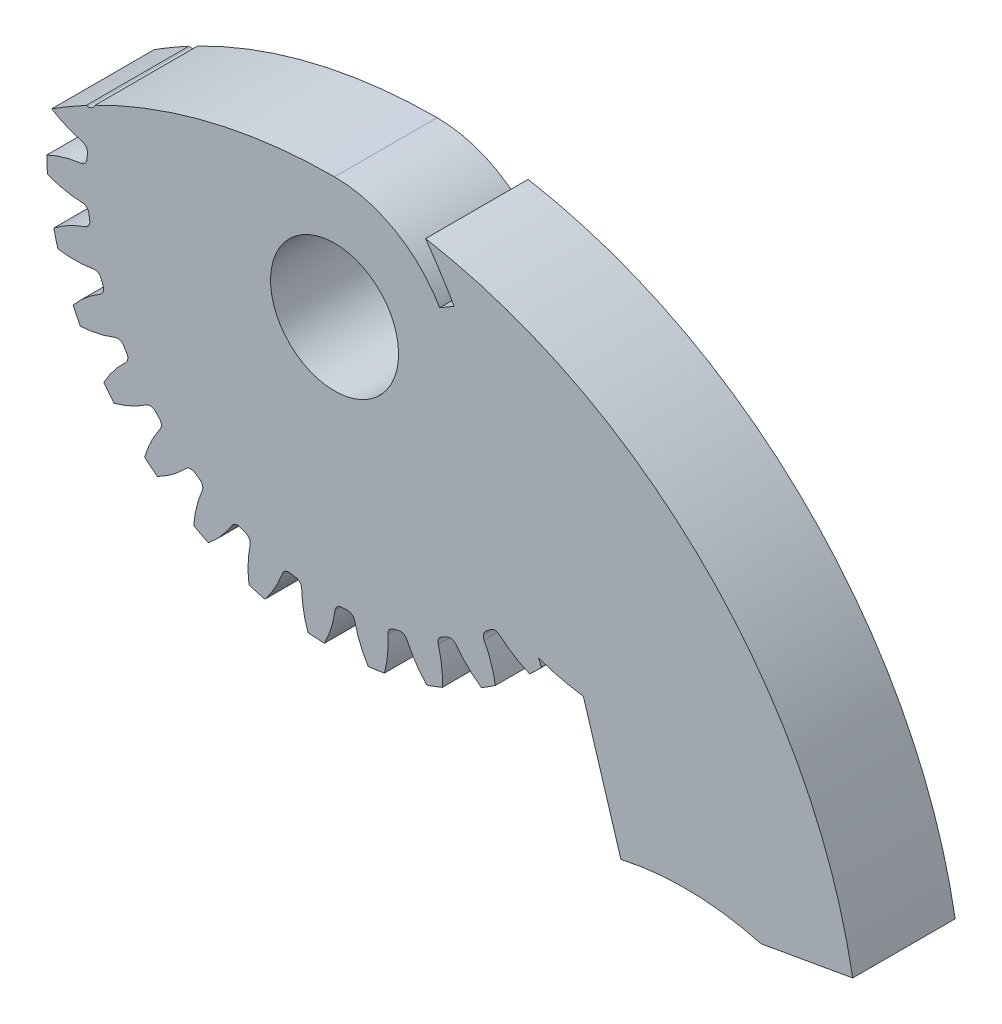
SolidWorks part; units mm, degrees
material "ABS"
ref_plane "Front" through (0, 0, 0) normal (0, 0, 1) x (1, 0, 0)
ref_plane "Top" through (0, 0, 0) normal (0, 1, 0) x (1, 0, 0)
ref_plane "Right" through (0, 0, 0) normal (1, 0, 0) x (0, 0, -1)
sketch "Sketch3" plane through (0, 0, 0) normal (0, 0, 1) x (1, 0, 0)
  circle A0 centre (0, 0) radius 40.64
  dimension "od" = 81.28
extrude "gearBody" add sketch "Sketch3" along normal blind 9.652
sketch "Sketch2" plane through (0, 0, 0) normal (0, 0, 1) x (1, 0, 0)
  line L0 (0, 0) -> (34.0786, 14.1158) construction
  line L1 (45.4751, -11.4855) -> (0, 0) construction
  line L2 (0, 0) -> (36.3143, 0) construction
  line L3 (38.0972, -0.458) -> (37.8451, -4.4001) construction
  line L5 (37.9712, -2.4291) -> (0, 0) construction
  line L7 (0, 0) -> (36.8864, 0) construction
  arc A0 (36.879, -0.7403) -> (36.6727, -3.9649) centre (0, 0) ccw construction
  arc A1 (40.637, 0.4947) -> (40.2427, -5.6687) centre (0, 0) ccw construction
  arc A2 (38.0972, -0.458) -> (37.8451, -4.4001) centre (0, 0) ccw construction
  arc A3 (34.9015, -2.6404) -> (34.9534, -1.8283) centre (0, 0) ccw
  arc A4 (45.4751, -11.4855) -> (35.6466, -3.6712) centre (32.0022, -18.3431) ccw
  arc A5 (45.4751, -11.4855) -> (46.5679, 5.5974) centre (0, 0) ccw
  arc A6 (46.5679, 5.5974) -> (35.8238, -0.9008) centre (34.0786, 14.1158) cw
  arc A7 (34.9534, -1.8283) -> (35.8238, -0.9008) centre (35.9376, -1.8798) cw
  arc A8 (35.6466, -3.6712) -> (34.9015, -2.6404) centre (35.8842, -2.7147) cw
  point P6 (46.5679, 5.5974)
  point P22 (45.4751, -11.4855)
  dimension "baseDia" = 73.7729
  dimension "od" = 81.28
  dimension "pd" = 76.2
  dimension "rd" = 70.0024
  dimension "rFillet" = 0.9855
  dimension "pointX" = 46.5679
  dimension "pointY" = 5.5974
  dimension "CTT" = 3.9421
  dimension "flankCenterAngle" = 22.5
extrude "toothCut" cut sketch "Sketch2" along normal through all
pattern_circular "CirPattern1" count 30 over 360 about axis through (0, 0, 9.652) along (0, 0, -1) of "toothCut"
scale "Scale1" scale about centroid uniform scaling no x scale factor 0.666667 y scale factor 0.666667 z scale factor 1
sketch "hub1Dia" plane through (0, 0, 0) normal (0, 0, -1) x (-1, 0, 0)
  circle A0 centre (0, 0) radius 12.7
  dimension "hub1Dia" = 25.4
sketch "hub2Dia" plane through (0, 0, 9.652) normal (0, 0, 1) x (1, 0, 0)
  circle A0 centre (0, 0) radius 12.7
  dimension "hub2dia" = 25.4
sketch "boreDia" plane through (0, 0, 0) normal (0, 0, 1) x (1, 0, 0)
  circle A0 centre (0, 0) radius 6.0255
  dimension "boreDia" = 12.051
extrude "bore" cut sketch "boreDia" against normal mid plane 25400
sketch "Sketch4" plane through (0, 0, 9.652) normal (0, 0, 1) x (1, 0, 0)
  circle A0 centre (0, -38.1) radius 49.53
  arc A2 (-27.1267, 3.3411) -> (27.1267, 3.3411) centre (0, 0) cw
  dimension "D1" = 99.06
  dimension "D2" = 38.1
extrude "Cut-Extrude1" cut sketch "Sketch4" against normal through all contours A0 region at (0, 16.3548, 9.652)
sketch "Sketch5" plane through (0, 0, 9.652) normal (0, 0, 1) x (1, 0, 0)
  line L0 (0, -38.1) -> (49.53, -38.1) construction
  line L1 (0, 0) -> (0, -38.1) construction
  line L2 (0, -38.1) -> (-24.765, 4.7942) construction
  line L3 (0, -38.1) -> (42.8942, -62.865) construction
  line L4 (23.4248, -19.2156) -> (26.9592, -30.742)
  line L6 (48.7775, -29.4992) -> (0, -38.1) construction
  line L7 (40.1449, -31.0214) -> (48.7775, -29.4992)
  circle A0 centre (0, -38.1) radius 49.53 construction
  circle A2 centre (0, -38.1) radius 14.3933 construction
  circle A3 centre (32.9956, -57.15) radius 27.0891 construction
  arc A4 (26.9592, -30.742) -> (40.1449, -31.0214) centre (32.9956, -57.15) cw
  arc A5 (48.7775, -29.4992) -> (8.0038, 10.779) centre (0, -38.1) ccw
  arc A6 (24.6567, 4.8566) -> (-22.5513, 5.9983) centre (0, -38.1) ccw construction
  spline S0 degree 2 poles (8.0038, 10.779) (4.7007, -16.4877) (23.4248, -19.2156) knots 0 0 0 1 1 1
  dimension "D2" = 28.7867
  dimension "D4" = 54.1782
  dimension "D1" = 120
  dimension "D3" = 120
  dimension "D5" = 38.1
  dimension "D6" = 80
extrude "Boss-Extrude1" add sketch "Sketch5" against normal up to surface (9.652 mm away) up to face at (6.0255, 0, 0)
sketch "Sketch6" plane through (0, 0, 9.652) normal (0, 0, 1) x (1, 0, 0)
  line L0 (0, 0) -> (-32.9956, -19.05) construction
  line L1 (0, 0) -> (0, -38.1) construction
  line L2 (-32.9956, -19.05) -> (0, 0) construction
  line L3 (11.2625, 6.5024) -> (9.8987, 5.715)
  circle A0 centre (-32.9956, -19.05) radius 49.53 construction
  circle A1 centre (-32.9956, -19.05) radius 51.1048 construction
  arc A3 (48.7775, -29.4992) -> (-22.5513, 5.9983) centre (0, -38.1) ccw construction
  arc A4 (11.2625, 6.5024) -> (8.5694, 10.6831) centre (-32.9956, -19.05) ccw
  circle A5 centre (0, -38.1) radius 49.53 construction
  arc A6 (8.5694, 10.6831) -> (0, 11.43) centre (0, -38.1) ccw
  arc A7 (9.8987, 5.715) -> (0, 11.43) centre (0, 0) ccw
  dimension "D1" = 99.06
  dimension "D4" = 102.2096
  dimension "D2" = 60
  dimension "D3" = 38.1
extrude "Body Tube Cut Out" cut sketch "Sketch6" against normal through all
equation "\"Aft_Section_Length\" = 32in"
equation "\"Mid_Coupler_Length\" = 12in"
equation "\"AB_Coupler_OD_Length\"= 1in"
equation "\"AB_Coupling_Section_Length\"= 0.375in"
equation "\"AB_Coupler_Length\"= \"AB_Coupler_OD_Length\" + \"AB_Coupling_Section_Length\" * 2"
equation "\"Cutout_Angle\" = 60"
equation "\"AB_Paddle_Height\" = 0.375in"
equation "\"AB_Coupler_Num_Screws\"= 4"
equation "\"Num_Cutouts\" = 4"
equation "\"AB_Coupler_OD\"= 4.024in"
equation "\"AB_Coupler_ID\"= 3.7in"
equation "\"AB_Coupler_Surface_Diameter\"= 3.899in"
equation "\"AB_Coupling_Screw_Diameter\"= 0.1065in"
equation "\"AB_Central_Bushing_Length\" = 0.75in"
equation "\"Lead_Screw_Dist\" = 2in"
equation "\"Lead_Screw_Diam\" = 0.375in"
equation "\"Lead_Screw_Length\" = \"Mid_Coupler_Length\" + 2*0.375in + 2*0.5in"
equation "\"Paddle_Pin_Offset\" = 0.25in"
equation "\"Paddle_Pin_Radius\" = 2.25*2/3in"
equation "\"Fwd_BKHD_From_Top\" = 18in"
equation "\"D1@Sketch4\"=\"Body_Tube_ID\""
equation "\"D2@Sketch4\"=\"Paddle_Pin_Radius\""
equation "\"Motor_OD\" = 54.4mm"
equation "\"Paddle_Gear_OD\" = 3.2in"
equation "\"Drive_Gear_OD\" = 1.7*2/3in"
equation "\"Fin_Thickness\" = 0.118in"
equation "\"DB9_Hole_Dist\" = 25mm"
equation "\"Motor_Length\" = 401mm"
equation "\"Body_Tube_OD\"= 4.024in"
equation "\"Body_Tube_ID\"= 3.90in"
equation "\"Coupler_OD\" = 3.899in"
equation "\"Coupler_ID\" = 3.755in"
equation "\"Fwd_Section_Length\" = 20in"
equation "\"Mid_Section_Length\" = 4in"
equation "\"Aft_Upper_Tube_Length\" = 10in"
equation "\"Aft_Lower_Tube_Length\" = 18in"
equation "\"Nosecone_Coupler_Length\" = 5in"
equation "\"Avionics_Bulkhead_Thickness\" = 0.25in"
equation "\"Avionics_Bulkhead_Lip\" = 0.125in"
equation "\"Avionics_Board_Length\" = \"Mid_Coupler_Length\" - 2*\"Avionics_Bulkhead_Lip\""
equation "\"Lead_Screw_Hole_Diam\" = 0.386in"
equation "\"Centering_Ring_Cutout_Dia\"=1.5in"
equation "\"Airbrakes_Wire_Hole_Dist\" = 1.1*2/3in"
equation "\"Airbrakes_Wire_Hole_Dia\" = 0.25in"
equation "\"DB9_Relief_Width\" = 0.47in"
equation "\"DB9_Relief_Hole_Offset\" = 0.09in"
equation "\"Servo_Gear_Offset\" = 0.5in"
equation "\"D2@Sketch5\"=\"Drive_Gear_OD\""
equation "\"D5@Sketch5\"=\"Paddle_Pin_Radius\""
equation "\"D1@Sketch6\"=\"Body_Tube_ID\""
equation "\"D2@Sketch6\"=60"
equation "\"D3@Sketch6\"=\"Paddle_Pin_Radius\""
equation "\"D4@Sketch6\"=\"Body_Tube_OD\""
equation "\"Airbrake_Shaft_Diameter\"= 12.051mm"
equation "\"boreDia@boreDia\"=\"Airbrake_Shaft_Diameter\""
